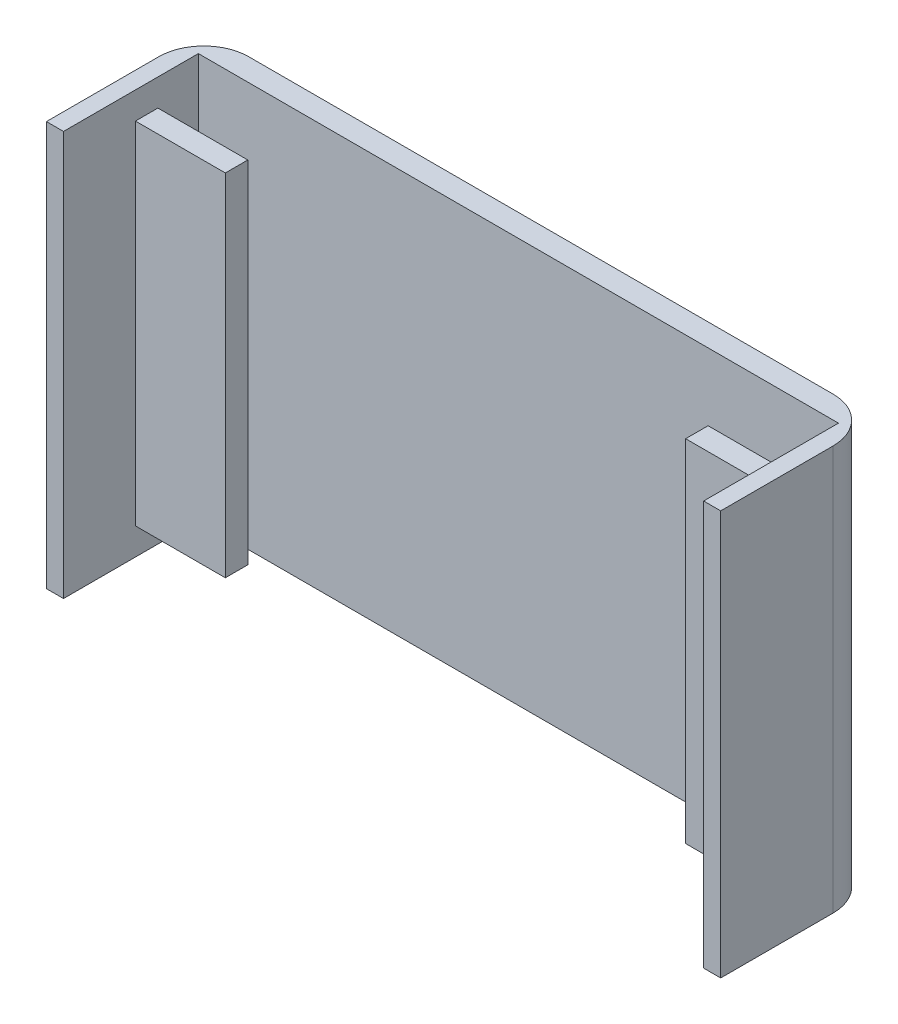
SolidWorks part; units mm, degrees
ref_plane "Front Plane" through (0, 0, 0) normal (0, 0, 1) x (1, 0, 0)
ref_plane "Top Plane" through (0, 0, 0) normal (0, 1, 0) x (1, 0, 0)
ref_plane "Right Plane" through (0, 0, 0) normal (1, 0, 0) x (0, 0, -1)
sketch "Sketch1" plane through (0, 0, 0) normal (0, 0, 1) x (1, 0, 0)
  line L1 (-75, 45) -> (75, 45)
  line L2 (-75, 45) -> (-75, -45)
  line L3 (-75, -45) -> (75, -45)
  line L4 (75, 45) -> (75, -45)
  line L5 (-75, 45) -> (75, -45) construction
  line L6 (-75, -45) -> (75, 45) construction
  point P0 (0, 0)
  point P6 (0, 0)
  dimension "D2" = 150
  dimension "D4" = 90
extrude "Boss-Extrude1" add sketch "Sketch1" along normal blind 5
sketch "Sketch2" plane through (0, 0, 5) normal (0, 0, 1) x (1, 0, 0)
  line L0 (-75, -45) -> (75, -45) construction
  line L1 (-75, 45) -> (-71.2, 45)
  line L2 (-75, 45) -> (-75, -45)
  line L3 (-75, -45) -> (-71.2, -45)
  line L4 (-71.2, 45) -> (-71.2, -45)
  line L5 (0, 0) -> (0, 45) construction
  line L6 (75, 45) -> (-75, 45) construction
  line L7 (75, -45) -> (71.2, -45)
  line L8 (71.2, 45) -> (71.2, -45)
  line L9 (75, 45) -> (71.2, 45)
  line L10 (75, 45) -> (75, -45)
  dimension "D1" = 3.8
extrude "Boss-Extrude2" add sketch "Sketch2" along normal blind 30
fillet "Fillet1" radius 10 2 edges at (-75, 0, 0) (75, 0, 0)
sketch "Sketch3" plane through (0, 45, 0) normal (0, 1, 0) x (1, 0, 0)
  line L0 (-71.2, -35) -> (-71.2, -5) construction
  line L1 (-71.2, -14) -> (-51.2, -14)
  line L2 (-71.2, -14) -> (-71.2, -19)
  line L3 (-71.2, -19) -> (-51.2, -19)
  line L4 (-51.2, -14) -> (-51.2, -19)
  line L5 (71.2, -35) -> (71.2, -5) construction
  line L6 (71.2, -14) -> (51.2, -14)
  line L7 (71.2, -14) -> (71.2, -19)
  line L8 (71.2, -19) -> (51.2, -19)
  line L9 (51.2, -14) -> (51.2, -19)
  line L10 (71.2, -5) -> (-71.2, -5) construction
  dimension "D1" = 9
  dimension "D2" = 9
  dimension "D3" = 5
  dimension "D4" = 5
  dimension "D5" = 20
  dimension "D6" = 20
extrude "Boss-Extrude3" add sketch "Sketch3" against normal up to surface (90 mm away) up to face at (0, -45, 16.5858)
sketch "Sketch4" plane through (0, 0, 19) normal (0, 0, 1) x (1, 0, 0)
  line L0 (71.2, -45) -> (71.2, 45) construction
  line L1 (-71.2, 45) -> (71.2, 45)
  line L2 (-71.2, 45) -> (-71.2, 39)
  line L3 (-71.2, 39) -> (71.2, 39)
  line L4 (71.2, 45) -> (71.2, 39)
  line L5 (0, 0) -> (-71.2, 0) construction
  line L6 (-71.2, -45) -> (-71.2, 45) construction
  line L7 (-71.2, -39) -> (71.2, -39)
  line L8 (71.2, -45) -> (71.2, -39)
  line L9 (-71.2, -45) -> (71.2, -45)
  line L10 (-71.2, -45) -> (-71.2, -39)
  dimension "D1" = 6
extrude "Cut-Extrude1" cut sketch "Sketch4" against normal blind 5
